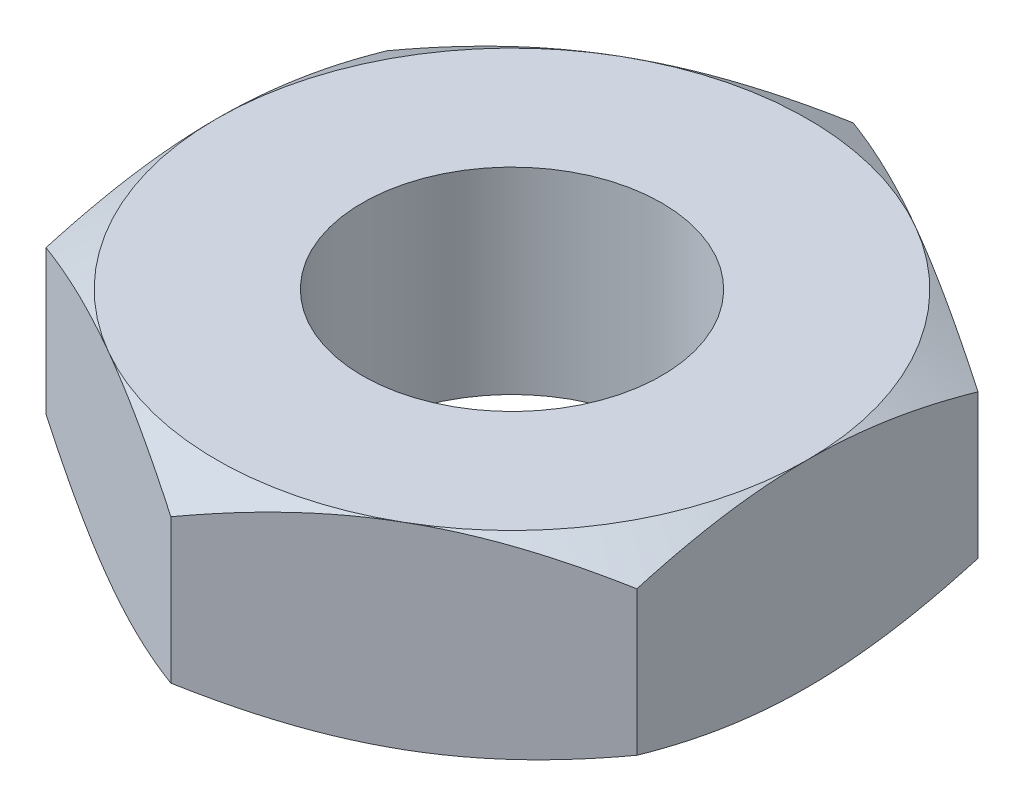
SolidWorks part; units mm, degrees
ref_plane "Front Plane" through (0, 0, 0) normal (0, 0, 1) x (1, 0, 0)
ref_plane "Top Plane" through (0, 0, 0) normal (0, 1, 0) x (1, 0, 0)
ref_plane "Right Plane" through (0, 0, 0) normal (1, 0, 0) x (0, 0, -1)
sketch "Sketch1" plane through (0, 0, 0) normal (0, 1, 0) x (1, 0, 0)
  line L1 (-4.7625, 2.7496) -> (-4.7625, -2.7496)
  line L2 (-4.7625, -2.7496) -> (0, -5.4993)
  line L3 (0, -5.4993) -> (4.7625, -2.7496)
  line L4 (4.7625, -2.7496) -> (4.7625, 2.7496)
  line L5 (4.7625, 2.7496) -> (0, 5.4993)
  line L6 (0, 5.4993) -> (-4.7625, 2.7496)
  circle A0 centre (0, 0) radius 4.7625 construction
  circle A1 centre (0, 0) radius 2.413
  dimension "Thread Size" = 4.826
  dimension "Hex" = 9.525
extrude "Boss-Extrude1" add sketch "Sketch1" along normal mid plane 3.175
sketch "Sketch2" plane through (0, 1.5875, 0) normal (0, 1, 0) x (1, 0, 0)
  circle A0 centre (0, 0) radius 2.413 construction
  circle A1 centre (0, 0) radius 2.413
curve "Helix/Spiral1" pitch 1.0583 height 4.2333 turns 4 parameters "Pitch"=1.0583
sketch "Sketch3" plane through (0, 0, 0) normal (1, 0, 0) x (0, 0, -1)
  line L0 (1.7256, 2.1167) -> (2.413, 2.5135)
  line L1 (2.413, 2.5135) -> (2.413, 1.5875)
  line L2 (2.413, 1.5875) -> (1.7256, 1.9844)
  line L3 (1.7256, 1.9844) -> (1.7256, 2.1167)
  line L4 (2.0693, 2.3151) -> (2.0693, 1.7859) construction
  line L5 (1.7256, 2.0505) -> (2.413, 2.0505) construction
  line L6 (2.413, 1.5875) -> (-2.413, 1.5875) construction
  dimension "D1" = 60
  dimension "D2" = 0.1323
  dimension "D3" = 0.5292
sweep "Sweep1" [suppressed] add profiles "Sketch3" path "Helix/Spiral1"
sketch "Sketch4" plane through (0, 1.5875, 0) normal (0, 1, 0) x (1, 0, 0)
  circle A1 centre (0, 0) radius 2.413
  circle A2 centre (0, 0) radius 2.413
  dimension "D1" = 0
extrude "Cut-Extrude1" [suppressed] cut sketch "Sketch4" along normal through all and the other way through all draft 45
sketch "Sketch5" plane through (0, 1.5875, 0) normal (0, 1, 0) x (1, 0, 0)
  circle A0 centre (0, 0) radius 4.7625 construction
  circle A1 centre (0, 0) radius 4.7625
extrude "Cut-Extrude2" cut sketch "Sketch5" against normal through all draft 60 flip side to cut
mirror "Mirror1" about plane through (0, 0, 0) normal (0, 1, 0) of "Cut-Extrude2", "Cut-Extrude1"
equation "\"D2@Sketch3\" = \"Pitch@Helix/Spiral1\"*.125"
equation "\"D3@Sketch3\" = \"Pitch@Helix/Spiral1\"*.5"
equation "\"D3@Helix/Spiral1\" = \"Height@Boss-Extrude1\"+\"Pitch@Helix/Spiral1\""
